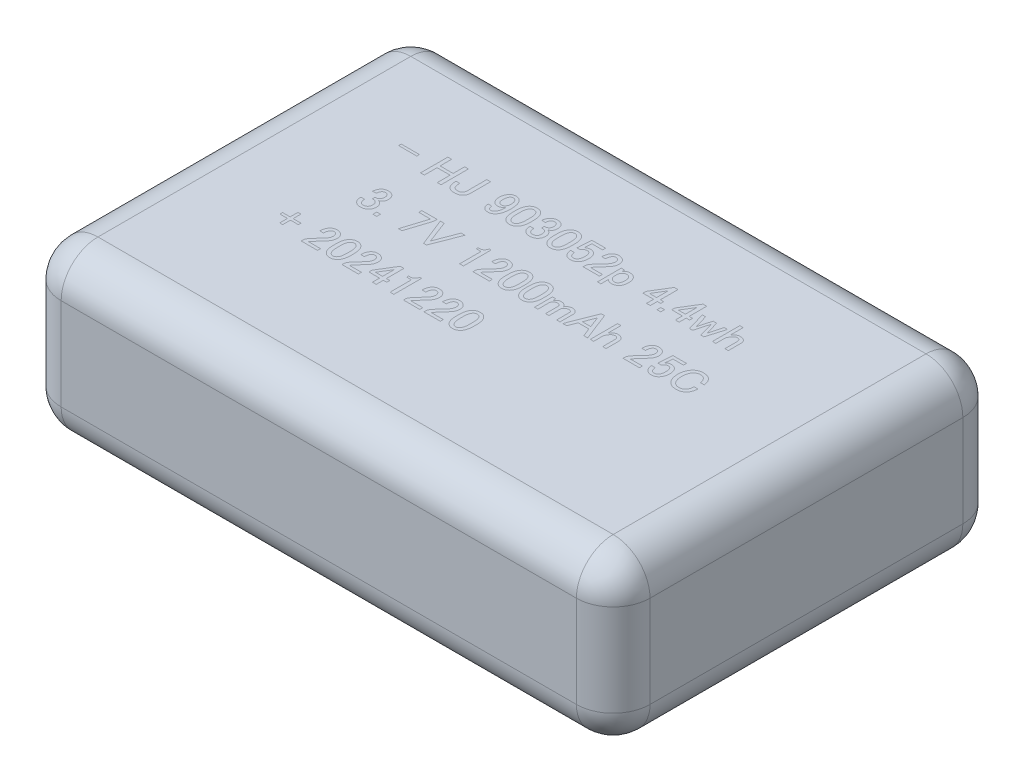
SolidWorks part; units mm, degrees
ref_plane "Front Plane" through (0, 0, 0) normal (0, 0, 1) x (1, 0, 0)
ref_plane "Top Plane" through (0, 0, 0) normal (0, 1, 0) x (1, 0, 0)
ref_plane "Right Plane" through (0, 0, 0) normal (1, 0, 0) x (0, 0, -1)
sketch "Sketch1" plane through (0, 0, 0) normal (0, 1, 0) x (1, 0, 0)
  line L1 (0, 0) -> (32, 0)
  line L2 (0, 0) -> (0, 21)
  line L3 (0, 21) -> (32, 21)
  line L4 (32, 0) -> (32, 21)
  dimension "D1" = 32
  dimension "D2" = 21
extrude "Boss-Extrude1" add sketch "Sketch1" along normal blind 9
fillet "Fillet1" radius 2 12 edges at (32, 4.5, -21) (32, 4.5, 0) (0, 4.5, -21) (0, 4.5, 0) (16, 0, 0) (32, 0, -10.5) (16, 0, -21) (0, 0, -10.5) (16, 9, -21) (32, 9, -10.5) (16, 9, 0) (0, 9, -10.5)
sketch "Sketch2" plane through (0, 9, 0) normal (0, 1, 0) x (1, 0, 0)
  text T0 "- HJ 903052p 4.4wh\r\n  3. 7V 1200mAh 25C\r\n+ 20241220" font "@MS UI Gothic" height 1.5
  point P1 (0, 0)
  point P2 (6.1151, 14.2025)
  point P3 (5.8051, 13.7548)
wrap "Wrap1" sketch "Sketch2" wrap type scribe source sketch "Sketch2" face at (16, 9, -10.5)
